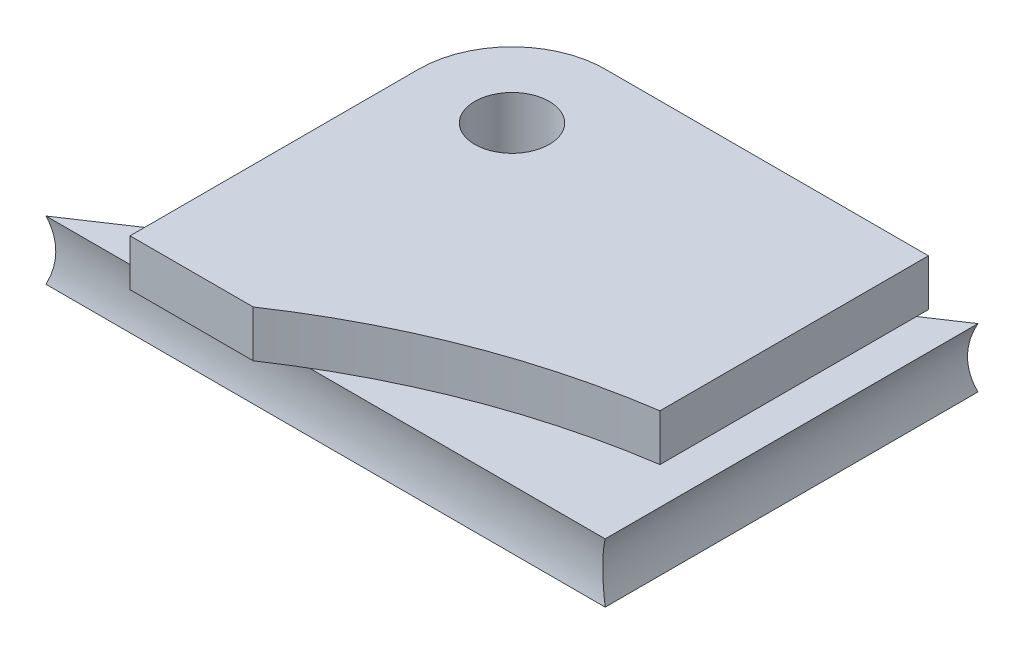
SolidWorks part; units mm, degrees
note: The reader was unsure of these and kept them because the rebuilt part matched: shared geometry of "Sketch1<3>".
ref_plane "Front Plane" through (0, 0, 0) normal (0, 0, 1) x (1, 0, 0)
ref_plane "Top Plane" through (0, 0, 0) normal (0, 1, 0) x (1, 0, 0)
ref_plane "Right Plane" through (0, 0, 0) normal (1, 0, 0) x (0, 0, -1)
sketch "Sketch1" plane through (0, 0, 0) normal (0, 1, 0) x (1, 0, 0)
  line L4 (30, 20) -> (-30, -20)
  line L6 (30, 20) -> (30, -20)
  line L8 (30, -20) -> (-30, -20)
  circle A0 centre (0, 0) radius 4
  circle A1 centre (0, 0) radius 10
  point P2 (0, 0)
  point P11 (97.9039, -15.5514)
  point P14 (0, 0)
  point P16 (43.7704, -20.0007)
  dimension "D2" = 20
  dimension "D3" = 8
  dimension "D1" = 40
  dimension "D4" = 60
extrude "Boss-Extrude1" add sketch "Sketch1" along normal blind 6.35
extrude "Boss-Extrude2" add sketch "Sketch1<3>" along normal blind 20 contours A1 A0 | L4 A1 A0
sketch "Sketch1<3>" plane through (0, 0, 0) normal (0, 1, 0) x (1, 0, 0) same geometry as "Sketch1"
ref_plane "Plane1" through (0, 10, 0) normal (0, 1, 0) x (1, 0, 0)
sketch "Sketch3" plane through (0, 0, 0) normal (0, 0, 1) x (1, 0, 0)
  line L0 (30, 3.175) -> (121.9702, 3.175) construction
  line L1 (30, 6.35) -> (30, 0) construction
  circle A0 centre (37.0901, 3.175) radius 7.7685
extrude "Cut-Extrude1" cut sketch "Sketch3" against normal through all both and the other way through all
sketch "Sketch4" plane through (0, 0, 0) normal (1, 0, 0) x (0, 0, -1)
  line L0 (-20, 3.175) -> (-60.4446, 3.175) construction
  line L1 (-20, 6.35) -> (-20, 0) construction
  circle A0 centre (-31.8039, 3.175) radius 12.2234
extrude "Cut-Extrude3" cut sketch "Sketch4" along normal through all both and the other way through all
sketch "Sketch5" plane through (0, 20, 0) normal (0, 1, 0) x (1, 0, 0)
  line L1 (-0.3116, 9.9951) -> (34.6884, 9.9951)
  line L4 (34.6884, 9.9951) -> (34.6884, -18.8136)
  line L7 (-10, 0) -> (-10, -30.9857)
  line L8 (-10, -30.9857) -> (3.2224, -30.9857)
  circle A0 centre (0, 0) radius 10 construction
  circle A1 centre (0, 0) radius 4
  arc A4 (3.2224, -30.9857) -> (34.6884, -18.8136) centre (45.7215, -94.0925) cw
  point P2 (34.8226, -22.6)
  point P10 (9.3343, -27.2747)
  point P12 (34.7246, -20.522)
  point P14 (34.6884, -18.8136)
  dimension "D1" = 35
extrude "Boss-Extrude3" add sketch "Sketch5" against normal blind 5
